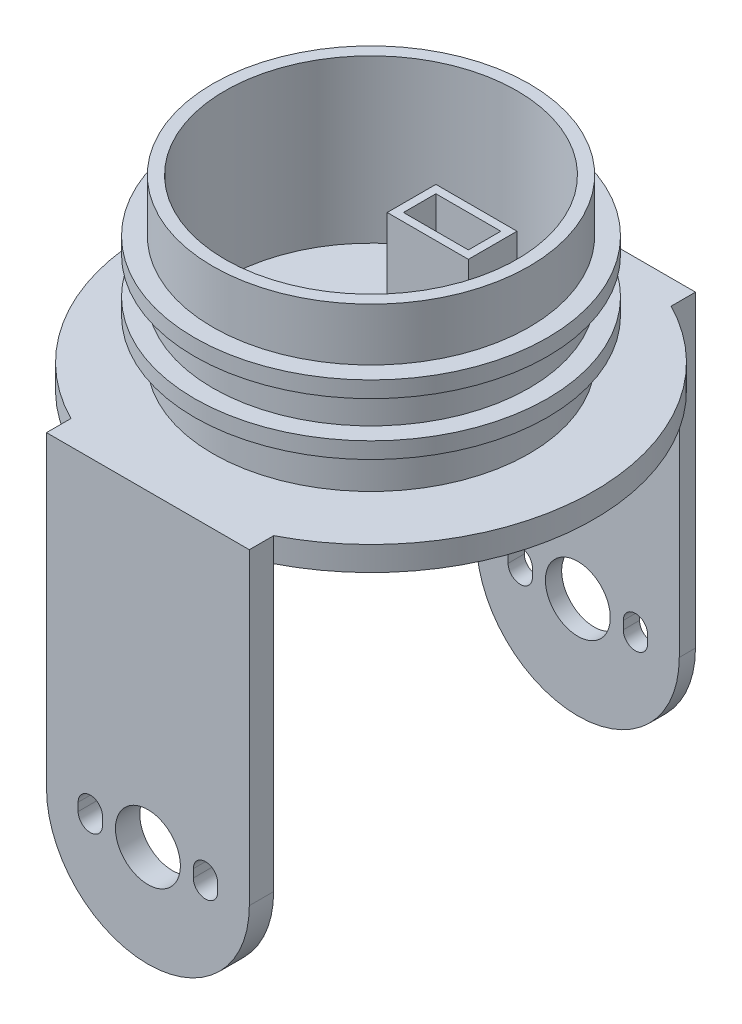
SolidWorks part; units mm, degrees
ref_plane "前基準面" through (0, 0, 0) normal (0, 0, 1) x (1, 0, 0)
ref_plane "上基準面" through (0, 0, 0) normal (0, 1, 0) x (1, 0, 0)
ref_plane "右基準面" through (0, 0, 0) normal (1, 0, 0) x (0, 0, -1)
sketch "草圖1" plane through (0, 0, 0) normal (0, 1, 0) x (1, 0, 0)
  circle A0 centre (0, 0) radius 19.5
  circle A1 centre (0, 0) radius 18
  dimension "D1" = 39
  dimension "D2" = 36
extrude "填料-伸長1" add sketch "草圖1" along normal blind 20
sketch "草圖3" plane through (0, 0, 0) normal (0, -1, 0) x (1, 0, 0)
  circle A0 centre (0, 0) radius 27.5
  dimension "D1" = 55
extrude "填料-伸長2" add sketch "草圖3" along normal blind 3
ref_plane "平面2" through (0, -3, 0) normal (0, -1, 0) x (-1, 0, 0)
ref_plane "平面5" through (0, 0, 0) normal (0, 1, 0) x (1, 0, 0)
ref_plane "平面6" through (0, 7, 0) normal (0, -1, 0) x (-1, 0, 0)
sketch "草圖25" plane through (0, 7, 0) normal (0, -1, 0) x (-1, 0, 0)
  circle A0 centre (0, 0) radius 21.75
  circle A1 centre (0, 0) radius 19.5
  dimension "D1" = 43.5
extrude "填料-伸長12" add sketch "草圖25" along normal blind 2
ref_plane "平面10" through (0, 10.5, 0) normal (0, -1, 0) x (-1, 0, 0)
sketch "草圖26" plane through (0, 10.5, 0) normal (0, -1, 0) x (-1, 0, 0)
  circle A0 centre (0, 0) radius 21.75
  circle A1 centre (0, 0) radius 19.5
extrude "填料-伸長13" add sketch "草圖26" against normal blind 2 from offset 1 offset against normal yes
sketch "草圖27" plane through (0, -3, 0) normal (0, -1, 0) x (1, 0, 0)
  line L0 (0, 0) -> (-12.5, 0)
  line L1 (46.0389, 0) -> (-46.0389, 0) construction
  line L2 (-12.5, 0) -> (-12.5, 25.5)
  line L3 (-12.5, 25.5) -> (12.5, 25.5)
  line L4 (12.5, 25.5) -> (12.5, 0)
  line L5 (12.5, 0) -> (-12.5, 0)
  line L6 (-12.5, 0) -> (-12.5, -25.5)
  line L7 (-12.5, -25.5) -> (12.5, -25.5)
  line L8 (12.5, -25.5) -> (12.5, 0)
  circle M6 centre (0, 0) radius 27.5
extrude "填料-伸長14" add sketch "草圖27" against normal blind 3 contours L8 L5 L0 L6 L7 M6 | L5 L4 L3 L2 L0 M6 | L6 L7 M6 | L7 L8 M6 | L4 L3 M6 | L3 L2 M6 region at (0, -3, -12.7084) region at (0, -3, 12.7084) region at (-11.7799, -3, 25.1714) region at (-11.7799, -3, -25.1714) region at (11.7799, -3, 25.1714) region at (11.7799, -3, -25.1714)
sketch "草圖28" plane through (0, 0, -25.5) normal (0, 0, -1) x (-1, 0, 0)
  line L0 (12.5, -3) -> (12.5, -38)
  line L1 (12.5, -38) -> (-12.5, -38)
  line L2 (-12.5, -38) -> (-12.5, 0)
  line L3 (-12.5, 0) -> (12.5, 0)
  line L4 (12.5, 0) -> (12.5, -3) construction
  line L5 (12.5, 0) -> (12.5, -3)
  line L6 (-7.1, -37.5) -> (-7.1, -38.5) construction
  line L7 (-5.6, -37.5) -> (-5.6, -38.5)
  line L8 (-8.6, -37.5) -> (-8.6, -38.5)
  line L9 (12.5, -3) -> (-12.5, -3)
  line L10 (7.1, -37.5) -> (7.1, -38.5) construction
  line L11 (8.6, -37.5) -> (8.6, -38.5)
  line L12 (5.6, -37.5) -> (5.6, -38.5)
  arc A0 (12.5, -38) -> (-12.5, -38) centre (0, -38) cw
  circle A1 centre (0, -38) radius 4
  arc A2 (-5.6, -37.5) -> (-8.6, -37.5) centre (-7.1, -37.5) ccw
  arc A3 (-8.6, -38.5) -> (-5.6, -38.5) centre (-7.1, -38.5) ccw
  arc A4 (8.6, -37.5) -> (5.6, -37.5) centre (7.1, -37.5) ccw
  arc A5 (5.6, -38.5) -> (8.6, -38.5) centre (7.1, -38.5) ccw
  point P14 (-7.1, -38)
  point P19 (-7.1, -36)
  point P20 (-7.1, -40)
  point P26 (7.1, -38)
  point P31 (7.1, -36)
  point P32 (7.1, -40)
  line M17 (10.2956, 0) -> (10.2956, -3)
  line M18 (10.2956, -3) -> (12.5, -3)
  line M19 (12.5, -3) -> (12.5, 0)
  line M20 (12.5, 0) -> (10.2956, 0)
  dimension "D1" = 8
  dimension "D2" = 4
  dimension "D3" = 3
  dimension "D4" = 5.6
  dimension "D5" = 4
  dimension "D6" = 3
  dimension "D7" = 5.6
  dimension "D8" = 35
extrude "填料-伸長17" add sketch "草圖28" along normal blind 2 contours A4 L11 L1 L0 L9 L2 L8 A2 L7 A1 L12 M18 | L9 L3 L2 M17 | M20 M17 M18 M19 | A5 L12 L1 A1 L7 A3 L8 A0 L11 region at (-11.3978, -1.5, -25.5) region at (0, -19.8277, -25.5) region at (0, -43.9487, -25.5) region at (1.1022, -1.5, -25.5)
extrude "填料-伸長19" add sketch "草圖28<15>" against normal blind 53 contours A4 L11 L1 L0 L9 L2 L8 A2 L7 A1 L12 M18 | A5 L12 L1 A1 L7 A3 L8 A0 L11 region at (0, -19.8277, -25.5) region at (0, -43.9487, -25.5)
sketch "草圖28<15>" plane through (0, 0, -25.5) normal (0, 0, -1) x (-1, 0, 0) same geometry as "草圖28"
sketch "草圖32" plane through (0, 0, 25.5) normal (0, 0, 1) x (1, 0, 0)
  line L0 (10.2956, -3) -> (12.5, -3)
  line L1 (-30.25, -3) -> (30.25, -3) construction
  line L2 (12.5, -3) -> (0, -3) construction
  line L3 (12.5, -3) -> (12.5, 0)
  line L4 (19.5, 0) -> (-19.5, 0) construction
  line L5 (12.5, 0) -> (12.5, -3) construction
  line L6 (12.5, 0) -> (10.2956, 0)
  line L7 (10.2956, 0) -> (10.2956, -3) construction
  line L8 (10.2956, 0) -> (10.2956, -3)
  line L9 (-10.2956, 0) -> (-10.2956, -3)
  line L10 (-10.2956, -3) -> (-10.2956, 0) construction
  line L11 (0, -3) -> (-12.5, -3) construction
  line L12 (-12.5, -3) -> (-10.2956, -3) construction
  line L13 (-10.2956, -3) -> (-12.5, -3)
  line L14 (-12.5, -3) -> (-12.5, 0)
  line L15 (-12.5, -3) -> (-12.5, 0) construction
  line L16 (-12.5, 0) -> (-10.2956, 0)
extrude "填料-伸長20" add sketch "草圖32" along normal blind 2
extrude "除料-伸長8" cut sketch "草圖28<18>" against normal blind 50 contours A4 L11 L1 L0 L9 L2 L8 A2 L7 A1 L12 M18 | A5 L12 L1 A1 L7 A3 L8 A0 L11 region at (0, -19.8277, -25.5) region at (0, -43.9487, -25.5)
sketch "草圖28<18>" plane through (0, 0, -25.5) normal (0, 0, -1) x (-1, 0, 0) same geometry as "草圖28"
sketch "草圖33" plane through (0, 0, 27.5) normal (0, 0, 1) x (1, 0, 0)
  line L0 (-12.5, -3) -> (12.5, -3)
  line L1 (-30.25, -3) -> (30.25, -3) construction
  line L2 (-12.5, -3) -> (-12.5, 0) construction
  line L3 (12.5, 0) -> (12.5, -3) construction
  line L4 (12.5, -3) -> (12.5, 0)
  line L5 (19.5, 0) -> (-19.5, 0) construction
  line L6 (12.5, 0) -> (-12.5, 0)
  line L7 (-12.5, 0) -> (-12.5, -3)
extrude "填料-伸長21" add sketch "草圖33" against normal blind 3
sketch "草圖34" plane through (0, 0, 0) normal (0, 1, 0) x (1, 0, 0)
  line L0 (0, 0) -> (-17.3838, 0) construction
  line L1 (-17.3838, 0) -> (19.1481, 0) construction
  line L2 (0, 0) -> (0, -21.2728) construction
  line L3 (0, -21.2728) -> (0, 19.1859) construction
  line L4 (5, 13) -> (-5, 13) construction
  line L5 (-4, 12) -> (4, 12)
  line L6 (-4, 12) -> (-4, 8)
  line L7 (-4, 8) -> (4, 8)
  line L8 (4, 12) -> (4, 8)
  line L10 (5, 7) -> (-5, 7)
  line L11 (5, 7) -> (5, 13)
  line L12 (5, 13) -> (-5, 13)
  line L13 (-5, 7) -> (-5, 13)
  point P12 (0, 0)
  point P13 (0, 13)
  dimension "D1" = 8
  dimension "D2" = 4
  dimension "D3" = 1
  dimension "D4" = 12
  dimension "D5" = 1
  dimension "D6" = 1
  dimension "D7" = 1
extrude "填料-伸長22" add sketch "草圖34" along normal blind 10
sketch "草圖38" plane through (0, 0, 0) normal (0, 1, 0) x (1, 0, 0)
  line L0 (-4, 12) -> (4, 12)
  line L1 (4, 12) -> (4, 8)
  line L2 (-4, 8) -> (4, 8) construction
  line L3 (-4, 8) -> (4, 8) construction
  line L4 (4, 8) -> (-4, 8)
  line L5 (-4, 8) -> (-4, 12)
extrude "除料-伸長9" cut sketch "草圖38" against normal blind 3
